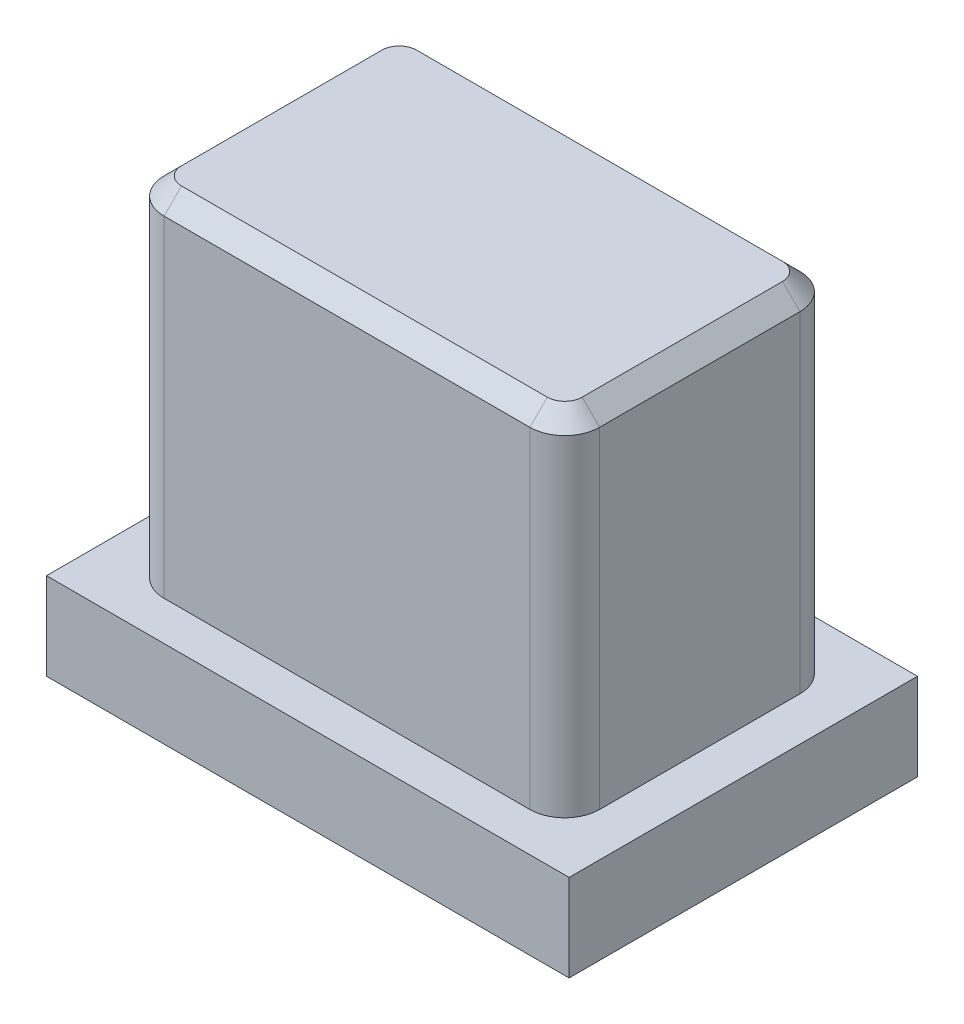
SolidWorks part; units mm, degrees
material "6061 Alloy"
ref_plane "Front Plane" through (0, 0, 0) normal (0, 0, 1) x (1, 0, 0)
ref_plane "Top Plane" through (0, 0, 0) normal (0, 1, 0) x (1, 0, 0)
ref_plane "Right Plane" through (0, 0, 0) normal (1, 0, 0) x (0, 0, -1)
sketch "jig_sketch" plane through (0, 0, 0) normal (0, 1, 0) x (1, 0, 0)
  line L1 (0, 0.8401) -> (25, 0.8401)
  line L2 (0, 0.8401) -> (0, 16.3401)
  line L3 (0, 16.3401) -> (25, 16.3401)
  line L4 (25, 0.8401) -> (25, 16.3401)
  line L5 (27.5, -1.4099) -> (-2.5, -1.4099)
  line L6 (27.5, -1.4099) -> (27.5, 18.5901)
  line L7 (-10.6625, 16.3401) -> (35.6625, 16.3401) construction
  line L8 (35.6625, 0.8401) -> (-10.6625, 0.8401) construction
  line L9 (27.5, 18.5901) -> (-2.5, 18.5901)
  line L10 (-2.5, -1.4099) -> (-2.5, 18.5901)
  line L11 (12.5, 18.5901) -> (12.5, -1.4099) construction
  line L12 (27.5, 8.5901) -> (-2.5, 8.5901) construction
  point P4 (0, 8.5901)
  point P5 (12.5, 0.8401)
  point P6 (-3.6721, 18.4825)
  point P9 (12.5, 8.5901)
  dimension "D1" = 25
  dimension "D2" = 20
  dimension "D3" = 30
extrude "insert" add sketch "jig_sketch" along normal blind 20 contours L1 L4 L3 L2 region at (12.5, 0, -8.5901)
extrude "base" add sketch "Sketch1<3>" against normal blind 5 contours L5 L10 L9 L6
sketch "Sketch1<3>" plane through (0, 0, 0) normal (0, 1, 0) x (1, 0, 0) same geometry as "jig_sketch"
fillet "round_edges" radius 2 4 edges at (25, 10, -0.8401) (25, 10, -16.3401) (0, 10, -16.3401) (0, 10, -0.8401)
chamfer "chamfer" distance 1 angle 45 8 edges at (12.5, 20, -16.3401) (0.5858, 20, -15.7543) (24.4142, 20, -15.7543) (0, 20, -8.5901) (25, 20, -8.5901) (0.5858, 20, -1.4259) (24.4142, 20, -1.4259) (12.5, 20, -0.8401)
